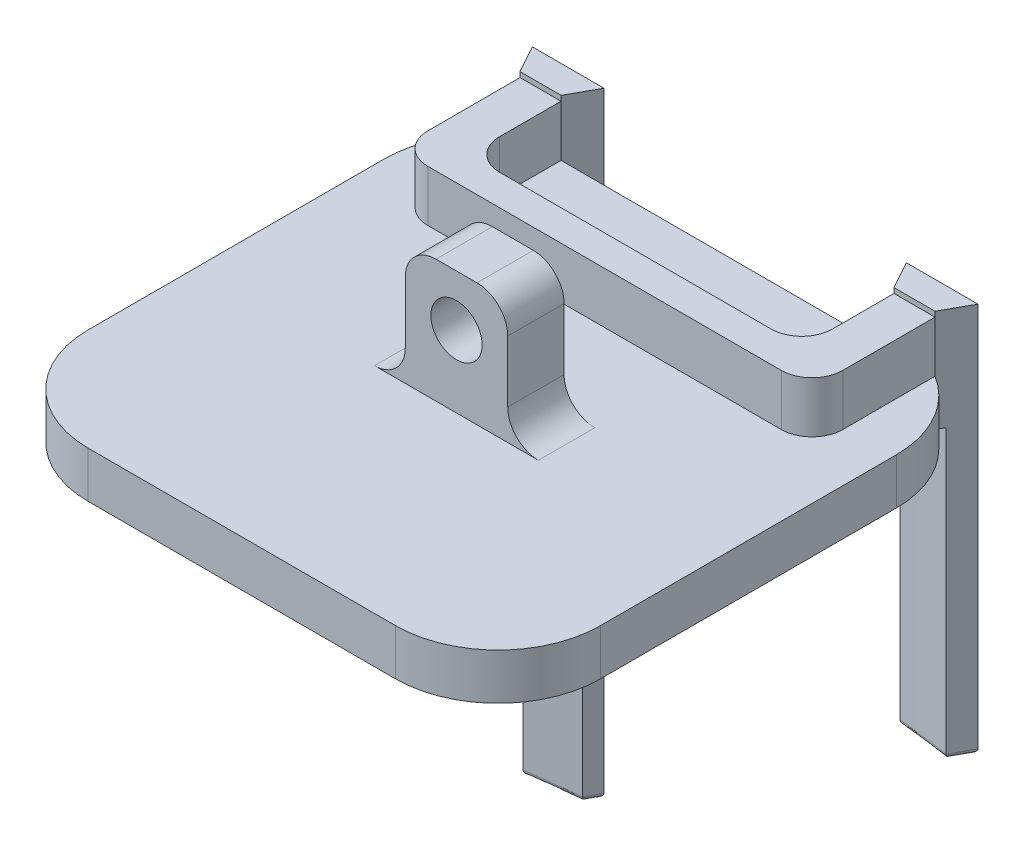
SolidWorks part; units mm, degrees
material "聚脂树脂"
ref_plane "前视基准面" through (0, 0, 0) normal (0, 0, 1) x (1, 0, 0)
ref_plane "上视基准面" through (0, 0, 0) normal (0, 1, 0) x (1, 0, 0)
ref_plane "右视基准面" through (0, 0, 0) normal (1, 0, 0) x (0, 0, -1)
other "Configuration Table"
sketch "草图1" plane through (0, 0, 0) normal (0, 1, 0) x (1, 0, 0)
  line L0 (0, 0) -> (0, 41.9379) construction
  line L1 (-25, -23.7) -> (25, -23.7)
  line L2 (-25, -23.7) -> (-25, 23.7)
  line L3 (-25, 23.7) -> (25, 23.7)
  line L4 (25, -23.7) -> (25, 23.7)
  line L5 (-25, -23.7) -> (25, 23.7) construction
  line L6 (-25, 23.7) -> (25, -23.7) construction
  line L7 (-20.25, 23.7) -> (-21.75, 26.4)
  line L8 (-21.75, 26.4) -> (-14.75, 26.4)
  line L9 (-14.75, 26.4) -> (-16.25, 23.7)
  line L10 (14.75, 26.4) -> (16.25, 23.7)
  line L11 (21.75, 26.4) -> (14.75, 26.4)
  line L12 (20.25, 23.7) -> (21.75, 26.4)
  point P0 (0, 0)
  dimension "D1" = 50
  dimension "D2" = 47.4
  dimension "D3" = 7
  dimension "D4" = 4
  dimension "D5" = 2.7
  dimension "D6" = 3.25
extrude "凸台-拉伸1" add sketch "草图1" along normal blind 4.5 contours L9 L8 L7 L3 | L3 L12 L11 L10 | L2 L1 L4 L3 region at (-18.25, 0, -25.1727) region at (18.25, 0, -25.1727)
sketch "草图2" plane through (0, 0, 0) normal (0, -1, 0) x (1, 0, 0)
  line L0 (-20.25, -23.7) -> (-16.25, -23.7)
  line L1 (16.25, -23.7) -> (20.25, -23.7)
  line L12 (-14.75, -26.4) -> (-16.25, -23.7)
  line L13 (-16.25, -23.7) -> (16.25, -23.7)
  line L14 (16.25, -23.7) -> (14.75, -26.4)
  line L15 (14.75, -26.4) -> (21.75, -26.4)
  line L16 (21.75, -26.4) -> (20.25, -23.7)
  line L17 (20.25, -23.7) -> (25, -23.7)
  line L18 (25, -23.7) -> (25, 23.7)
  line L19 (25, 23.7) -> (-25, 23.7)
  line L20 (-25, 23.7) -> (-25, -23.7)
  line L21 (-25, -23.7) -> (-20.25, -23.7)
  line L22 (-20.25, -23.7) -> (-21.75, -26.4)
  line L23 (-21.75, -26.4) -> (-14.75, -26.4)
  line L24 (-14.75, -26.4) -> (-16.25, -23.7)
  line L25 (-16.25, -23.7) -> (16.25, -23.7)
  line L26 (16.25, -23.7) -> (14.75, -26.4)
  line L27 (14.75, -26.4) -> (21.75, -26.4)
  line L28 (21.75, -26.4) -> (20.25, -23.7)
  line L29 (20.25, -23.7) -> (25, -23.7)
  line L30 (25, -23.7) -> (25, 23.7)
  line L31 (25, 23.7) -> (-25, 23.7)
  line L32 (-25, 23.7) -> (-25, -23.7)
  line L33 (-25, -23.7) -> (-20.25, -23.7)
  line L34 (-20.25, -23.7) -> (-21.75, -26.4)
  line L35 (-21.75, -26.4) -> (-14.75, -26.4)
  line M13 (-14.75, -26.4) -> (-16.25, -23.7)
  line M15 (16.25, -23.7) -> (14.75, -26.4)
  line M16 (14.75, -26.4) -> (21.75, -26.4)
  line M17 (21.75, -26.4) -> (20.25, -23.7)
  line M23 (-20.25, -23.7) -> (-21.75, -26.4)
  line M24 (-21.75, -26.4) -> (-14.75, -26.4)
  dimension "D1" = 0
extrude "凸台-拉伸2" add sketch "草图2" along normal blind 40 and the other way blind 10 contours L0 M23 M24 M13 | L1 M15 M16 M17 region at (-18.25, 0, -25.1727) region at (18.25, 0, -25.1727)
sketch "草图3" plane through (0, 0, 0) normal (0, -1, 0) x (1, 0, 0)
  line L0 (0, 0) -> (0, 71.645) construction
  line L1 (25, 23.7) -> (25, -23.7) construction
  line L2 (20.25, -23.7) -> (25, -23.7) construction
  line L3 (-25, -23.7) -> (25, -23.7)
  arc A0 (25, -23.7) -> (-25, -23.7) centre (0, 118.1133) cw
  dimension "D1" = 144
extrude "切除-拉伸1" cut sketch "草图3" along normal blind 111
fillet "圆角1" radius 10 2 edges at (25, 2.25, -23.7) (-25, 2.25, -23.7)
sketch "草图4" plane through (0, 4.5, 0) normal (0, 1, 0) x (1, 0, 0)
  line L0 (-20.25, 23.7) -> (-20.25, 11.7)
  line L1 (-20.25, 11.7) -> (-16.25, 11.7)
  line L2 (-16.25, 23.7) -> (-16.25, 11.7)
  line L3 (0, 0) -> (0, 27.1537) construction
  line L4 (-20.25, 23.7) -> (-16.25, 23.7)
  line L5 (20.25, 23.7) -> (20.25, 11.7)
  line L6 (20.25, 11.7) -> (16.25, 11.7)
  line L7 (16.25, 23.7) -> (16.25, 11.7)
  line L8 (20.25, 23.7) -> (16.25, 23.7)
  line L9 (-16.25, 11.7) -> (16.25, 11.7)
  line L10 (-16.25, 14.7) -> (16.25, 14.7)
  line M10 (20.25, 23.7) -> (16.25, 23.7)
  line M12 (-16.25, 23.7) -> (-20.25, 23.7)
  dimension "D1" = 12
  dimension "D2" = 3
extrude "凸台-拉伸3" add sketch "草图4" along normal blind 5 contours L2 L0 L1 M12 | L10 L2 L9 L7 | L7 L6 L5 M10 | L3 L9 L7 L10 region at (-18.25, 4.5, -17.7) region at (-8.125, 4.5, -13.2) region at (8.125, 4.5, -13.2) region at (18.25, 4.5, -17.7)
fillet "圆角2" radius 10 2 edges at (-25, 2.25, 23.7) (25, 2.25, 23.7)
sketch "草图5" plane through (0, 4.5, 0) normal (0, 1, 0) x (1, 0, 0)
  line L0 (0, 0) -> (0, 8.5694) construction
  line L1 (-5, -2.75) -> (5, -2.75)
  line L2 (-5, -2.75) -> (-5, 2.75)
  line L3 (-5, 2.75) -> (5, 2.75)
  line L4 (5, -2.75) -> (5, 2.75)
  line L5 (-5, -2.75) -> (5, 2.75) construction
  line L6 (-5, 2.75) -> (5, -2.75) construction
  point P0 (0, 0)
  dimension "D1" = 10
  dimension "D2" = 5.5
  dimension "D3" = 0
extrude "凸台-拉伸4" add sketch "草图5" along normal blind 12
sketch "草图6" plane through (0, 0, 2.75) normal (0, 0, 1) x (1, 0, 0)
  line L0 (-5, 16.5) -> (5, 16.5) construction
  line L1 (-5, 16.5) -> (-5, 4.5) construction
  circle A0 centre (0, 11.5) radius 2.5
  dimension "D1" = 5
  dimension "D2" = 5
  dimension "D3" = 5
extrude "切除-拉伸2" cut sketch "草图6" against normal blind 6
fillet "圆角3" radius 3 4 edges at (-5, 16.5, 0) (5, 16.5, 0) (5, 4.5, 0) (-5, 4.5, 0)
fillet "圆角4" radius 3 4 edges at (16.25, 7, -14.7) (-16.25, 7, -14.7) (20.25, 7, -11.7) (-20.25, 7, -11.7)
sketch "草图7" plane through (0, -40, 0) normal (0, -1, 0) x (1, 0, 0)
  line L3 (-14.75, -26.4) -> (-15.4999, -25.0501)
  line L4 (-20.6389, -24.4) -> (-21.75, -26.4)
  line L5 (-21.75, -26.4) -> (-14.75, -26.4)
  line L6 (-14.75, -26.4) -> (-15.4999, -25.0501)
  line L7 (-20.6389, -24.4) -> (-21.75, -26.4)
  line L8 (-21.75, -26.4) -> (-14.75, -26.4)
  arc A1 (-20.6389, -24.4) -> (-15.4999, -25.0501) centre (0, 118.1133) ccw
  arc A2 (-20.6389, -24.4) -> (-15.4999, -25.0501) centre (0, 118.1133) ccw
  dimension "D1" = 0
extrude "凸台-拉伸5" add sketch "草图7" along normal blind 10
sketch "草图8" plane through (0, 0, -26.4) normal (0, 0, -1) x (-1, 0, 0)
  line L0 (-21.75, -28) -> (-14.75, -28)
  line L1 (-21.75, 10) -> (-21.75, -40) construction
  line L2 (-14.75, 10) -> (-14.75, -40) construction
  line L3 (-14.75, -28) -> (-14.75, -40)
  line L4 (-14.75, -40) -> (-21.75, -40)
  line L5 (-21.75, -40) -> (-21.75, -28)
  dimension "D1" = 12
extrude "切除-拉伸3" cut sketch "草图8" against normal blind 11.8
fillet "圆角5" radius 0.4 8 edges at (-21.1945, -50, -25.4) (-18.0723, -50, -24.7482) (-15.125, -50, -25.7251) (-18.25, -50, -26.4) (21.1945, -28, -25.4) (18.25, -28, -26.4) (15.125, -28, -25.7251) (18.0723, -28, -24.7482)
